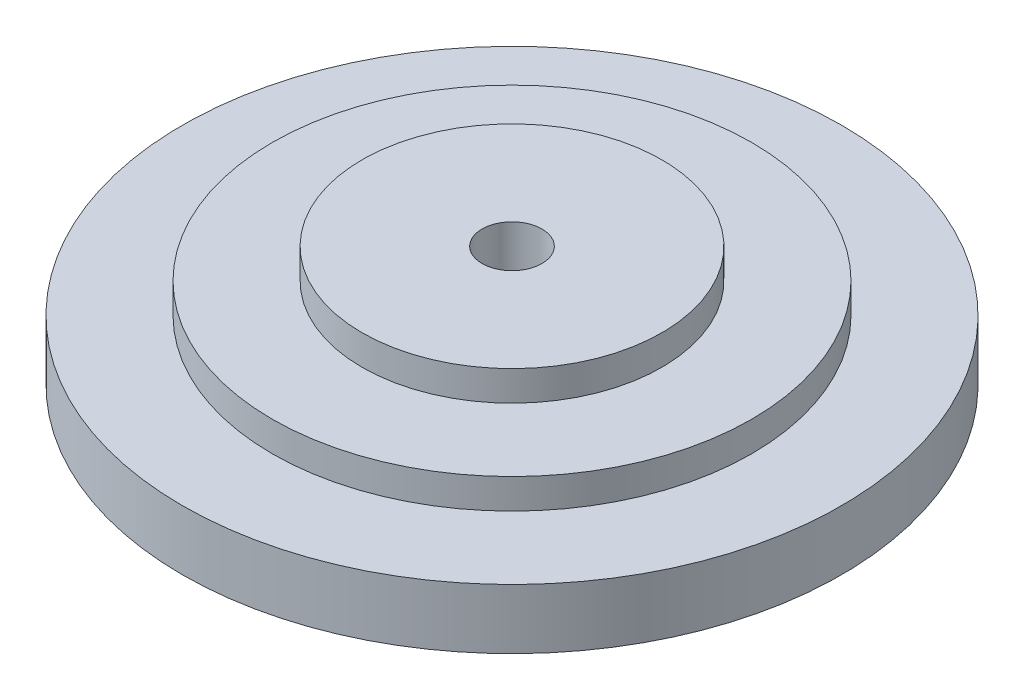
SolidWorks part; units mm, degrees
ref_plane "Piano frontale" through (0, 0, 0) normal (0, 0, 1) x (1, 0, 0)
ref_plane "Piano superiore" through (0, 0, 0) normal (0, 1, 0) x (1, 0, 0)
ref_plane "Piano destro" through (0, 0, 0) normal (1, 0, 0) x (0, 0, -1)
sketch "Schizzo2" plane through (0, 0, 0) normal (0, 1, 0) x (1, 0, 0)
  circle A0 centre (0, 0) radius 25.0225
  circle A1 centre (0, 0) radius 40.0225
  circle A2 centre (0, 0) radius 55.0225
  circle A3 centre (0, 0) radius 5
  dimension "D1" = 50.045
  dimension "D2" = 80.045
  dimension "D3" = 110.045
  dimension "D4" = 10
extrude "Estrusione-Estrusione1" add sketch "Schizzo2" along normal blind 10 contours A2 A1 region at (-53.4662, 0, 0)
extrude "Estrusione-Estrusione2" add sketch "Schizzo2<3>" along normal blind 15 contours A1 A0 region at (-38.8905, 0, 0)
sketch "Schizzo2<3>" plane through (0, 0, 0) normal (0, 1, 0) x (1, 0, 0) same geometry as "Schizzo2"
extrude "Estrusione-Estrusione3" add sketch "Schizzo2<4>" along normal blind 20 contours A0 A3 region at (-24.3148, 0, 0)
sketch "Schizzo2<4>" plane through (0, 0, 0) normal (0, 1, 0) x (1, 0, 0) same geometry as "Schizzo2"
equation "\"k\"= 0.045mm'kerf"
equation "\"w\"= 30mm'circle width"
equation "\"m\"= 5.7mm'material thickness"
equation "\"jhf\"= \"m\" - 2 * \"k\"'female joint height"
equation "\"jhm\"= \"m\" + 2 * \"k\"'male joint height"
equation "\"d\"= 50mm'circle diameter"
equation "\"d2\"= \"d\" + 30mm"
equation "\"d3\"= \"d2\" + 30mm"
equation "\"id\"= 40mm 'internal circle distance"
equation "\"D1@Schizzo2\"=\"d\"+ \"k\""
equation "\"D3@Schizzo2\"= \"d3\"+ \"k\""
equation "\"D2@Schizzo2\"=\"d2\"+ \"k\""
